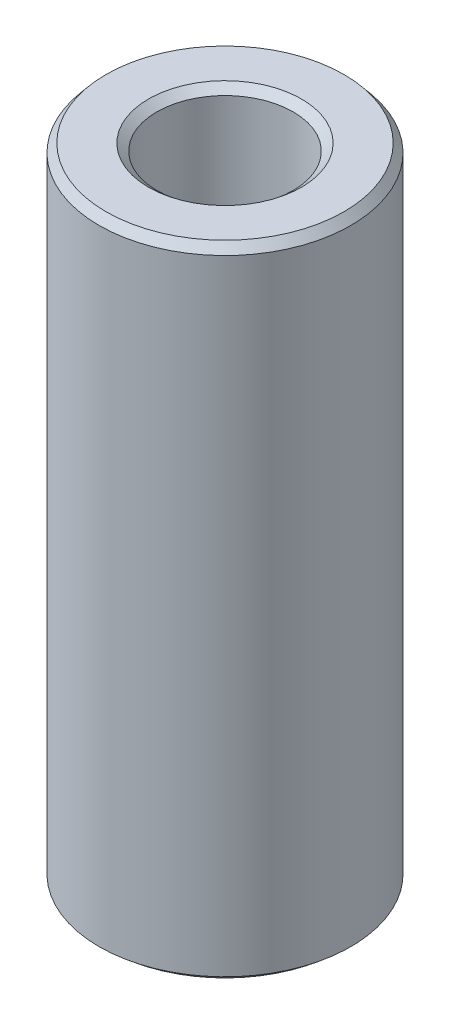
SolidWorks part; units mm, degrees
ref_plane "Front Plane" through (0, 0, 0) normal (0, 0, 1) x (1, 0, 0)
ref_plane "Top Plane" through (0, 0, 0) normal (0, 1, 0) x (1, 0, 0)
ref_plane "Right Plane" through (0, 0, 0) normal (1, 0, 0) x (0, 0, -1)
sketch "Sketch1" plane through (0, 0, 0) normal (0, 1, 0) x (1, 0, 0)
  circle A0 centre (0, 0) radius 50
  dimension "SLEEVE_OD" = 100
extrude "Boss-Extrude1" add sketch "Sketch1" along normal blind 254.1354
sketch "Sketch2" plane through (0, 0, 0) normal (0, 1, 0) x (1, 0, 0)
  circle A0 centre (0, 0) radius 27.0574
  dimension "BORE_D" = 54.1148
extrude "Cut-Extrude1" cut sketch "Sketch2" along normal through all
chamfer "Chamfer1" distance 3.3225 angle 39.75 4 edges at (0, 254.1354, 27.0574) (0, 0, 27.0574) (0, 0, 50) (0, 254.1354, 50) first distance on face at (0, 254.1354, 27.0574) first distance on face at (0, 0, 27.0574) first distance on face at (0, 254.1354, 50)
